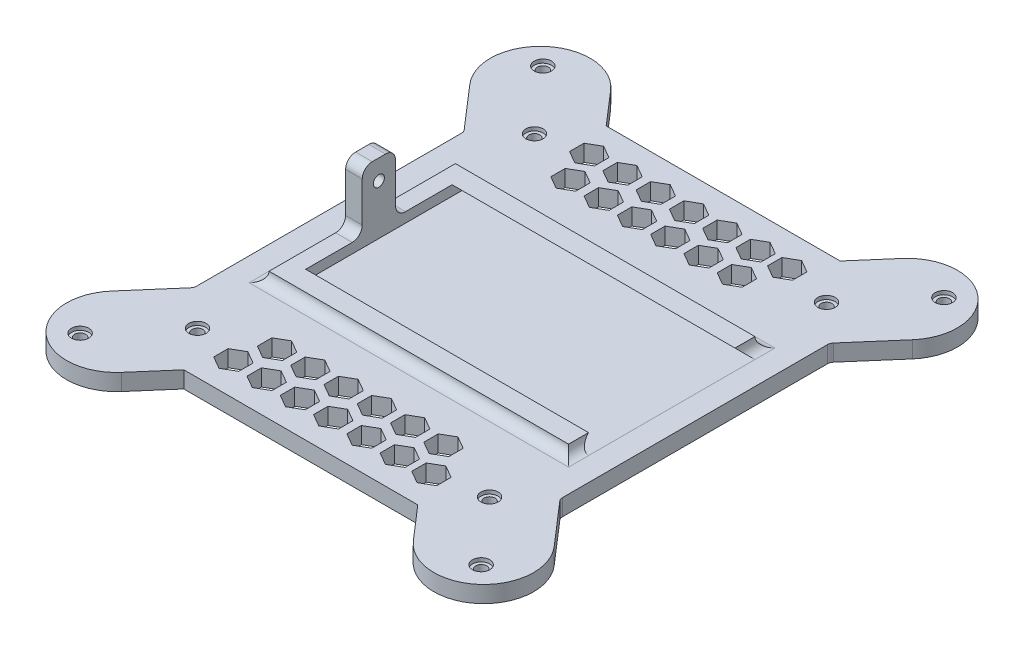
SolidWorks part; units mm, degrees
ref_plane "Front Plane" through (0, 0, 0) normal (0, 0, 1) x (1, 0, 0)
ref_plane "Top Plane" through (0, 0, 0) normal (0, 1, 0) x (1, 0, 0)
ref_plane "Right Plane" through (0, 0, 0) normal (1, 0, 0) x (0, 0, -1)
sketch "Sketch1" plane through (0, 0, 0) normal (0, 1, 0) x (1, 0, 0)
  line L0 (-53.6647, 84.824) -> (-76.3353, 65.176)
  line L1 (-65, 75) -> (65, 75) construction
  line L2 (-65, 75) -> (-65, -75) construction
  line L3 (-65, -75) -> (65, -75) construction
  line L4 (65, 75) -> (65, -75) construction
  line L5 (-65, 75) -> (65, -75) construction
  line L6 (-65, -75) -> (65, 75) construction
  line L7 (-76.3353, 65.176) -> (53.6647, -84.824)
  line L8 (53.6647, -84.824) -> (76.3353, -65.176)
  line L9 (76.3353, -65.176) -> (-53.6647, 84.824)
  line L10 (53.6647, 84.824) -> (76.3353, 65.176)
  line L11 (76.3353, 65.176) -> (-53.6647, -84.824)
  line L12 (-53.6647, -84.824) -> (-76.3353, -65.176)
  line L13 (-76.3353, -65.176) -> (53.6647, 84.824)
  line L15 (-55, -63.4615) -> (55, -63.4615)
  line L16 (-55, -63.4615) -> (-55, 63.4615)
  line L17 (-55, 63.4615) -> (55, 63.4615)
  line L18 (55, -63.4615) -> (55, 63.4615)
  line L19 (-55, -63.4615) -> (55, 63.4615) construction
  line L20 (-55, 63.4615) -> (55, -63.4615) construction
  point P0 (0, 0)
  point P12 (0, 0)
  dimension "D1" = 130
  dimension "D2" = 150
  dimension "D3" = 30
  dimension "D4" = 30
  dimension "D5" = 110
extrude "Boss-Extrude1" add sketch "Sketch1" along normal blind 5 contours L16 L17 L9 L0 L7 | L16 L13 L7 | L17 L16 L7 L13 L9 | L17 L9 L13 | L18 L11 L10 L13 L17 | L11 L18 L17 L13 L9 | L9 L18 L11 | L15 L18 L9 L11 L7 | L18 L15 L7 L8 L9 | L11 L15 L7 | L13 L7 L11 L9 | L16 L15 L11 L7 L13 | L15 L16 L13 L12 L11 region at (-57.5786, 0, -65.7171) region at (0, 0, -49.9421) region at (-30.0835, 0, -34.7117) region at (-43.2831, 0, 0) region at (30.0835, 0, -34.7117) region at (0, 0, 0) region at (57.5786, 0, -65.7171) region at (-30.0835, 0, 34.7117) region at (-57.5786, 0, 65.7171) region at (43.2831, 0, 0) region at (30.0835, 0, 34.7117) region at (0, 0, 49.9421) region at (57.5786, 0, 65.7171)
sketch "Sketch2" plane through (0, 0, 0) normal (0, -1, 0) x (1, 0, 0)
  line L0 (-65, 75) -> (65, -75) construction
  line L1 (-53.6647, 84.824) -> (-76.3353, 65.176) construction
  line L2 (53.6647, -84.824) -> (76.3353, -65.176) construction
  line L3 (65, 75) -> (-65, -75) construction
  line L4 (53.6647, 84.824) -> (76.3353, 65.176) construction
  line L5 (-53.6647, -84.824) -> (-76.3353, -65.176) construction
  circle A0 centre (-60.2536, 69.5234) radius 1.65
  circle A1 centre (-43.8803, 50.6312) radius 1.65
  circle A2 centre (60.2536, 69.5234) radius 1.65
  circle A3 centre (43.8803, 50.6312) radius 1.65
  circle A4 centre (60.2536, -69.5234) radius 1.65
  circle A5 centre (43.8803, -50.6312) radius 1.65
  circle A6 centre (-60.2536, -69.5234) radius 1.65
  circle A7 centre (-43.8803, -50.6312) radius 1.65
  point P43 (0, 0)
  dimension "D2" = 3.3
  dimension "D1" = 25
  dimension "D3" = 67
extrude "Cut-Extrude1" cut sketch "Sketch2" against normal up to surface (5 mm away) up to face at (0, 5, 0)
fillet "Fillet1" 2 edges at (76.3353, 2.5, 65.176) (53.6647, 2.5, 84.824) type full round first side face at (65.6677, 2.5, 52.8672) second side face at (44.4076, 2.5, 74.1427) middle face at (65, 2.5, 75)
fillet "Fillet2" 2 edges at (-53.6647, 2.5, 84.824) (-76.3353, 2.5, 65.176) type full round first side face at (-44.4076, 2.5, 74.1427) second side face at (-65.6677, 2.5, 52.8672) middle face at (-65, 2.5, 75)
fillet "Fillet3" 2 edges at (-76.3353, 2.5, -65.176) (-53.6647, 2.5, -84.824) type full round first side face at (-65.6677, 2.5, -52.8672) second side face at (-44.4076, 2.5, -74.1427) middle face at (-65, 2.5, -75)
fillet "Fillet4" 2 edges at (53.6647, 2.5, -84.824) (76.3353, 2.5, -65.176) type full round first side face at (44.4076, 2.5, -74.1427) second side face at (65.6677, 2.5, -52.8672) middle face at (65, 2.5, -75)
sketch "Sketch4" plane through (0, 5, 0) normal (0, 1, 0) x (1, 0, 0)
  circle A0 centre (-60.2536, 69.5234) radius 2.6
  circle A1 centre (-43.8803, 50.6312) radius 2.6
  circle A2 centre (43.8803, 50.6312) radius 2.6
  circle A3 centre (60.2536, 69.5234) radius 2.6
  circle A4 centre (43.8803, -50.6312) radius 2.6
  circle A5 centre (60.2536, -69.5234) radius 2.6
  circle A6 centre (-43.8803, -50.6312) radius 2.6
  circle A7 centre (-60.2536, -69.5234) radius 2.6
  dimension "D1" = 5.2
extrude "Cut-Extrude3" cut sketch "Sketch4" against normal blind 1.1
fillet "Fillet6" radius 2 4 edges at (55, 2.5, 40.5583) (55, 2.5, -40.5583) (-55, 2.5, -40.5583) (-55, 2.5, 40.5583)
sketch "Sketch8" plane through (55, 0, 0) normal (1, 0, 0) x (0, 0, -1)
  line L0 (-28, 8.0001) -> (-28, 5)
  line L1 (-39.8123, 5) -> (39.8123, 5) construction
  line L2 (-28, 5) -> (28, 5)
  line L3 (28, 5) -> (28, 8.0001)
  line L4 (28, 8.0001) -> (22, 8.0001)
  line L5 (22, 8.0001) -> (25, 5.0001)
  line L6 (25, 5.0001) -> (-25, 5.0001)
  line L7 (-25, 5.0001) -> (-22, 8.0001)
  line L8 (-22, 8.0001) -> (-28, 8.0001)
  line L11 (-39.8123, 0) -> (39.8123, 0) construction
  point P7 (0, 5.0001)
  point P15 (0, 0)
  dimension "D1" = 56
  dimension "D2" = 3.0001
  dimension "D3" = 45
  dimension "D4" = 45
  dimension "D5" = 3
  dimension "D6" = 3
  dimension "D7" = 3
  dimension "D8" = 3
extrude "Boss-Extrude3" add sketch "Sketch8" against normal blind 90 from offset 10 offset against normal yes
sketch "Sketch9" plane through (0, 0, -28) normal (0, 0, -1) x (-1, 0, 0)
  line L0 (45, 8.0001) -> (-45, 8.0001) construction
  line L1 (45, 5) -> (40, 5)
  line L2 (45, 5) -> (45, 8.0001)
  line L3 (45, 8.0001) -> (40, 8.0001)
  line L4 (40, 5) -> (40, 8.0001)
  line L5 (45, 5) -> (40, 8.0001) construction
  line L6 (45, 8.0001) -> (40, 5) construction
  line L7 (45, 5) -> (45, 8.0001) construction
  line L8 (45, 5) -> (-45, 5) construction
  point P0 (42.5, 6.5001)
  dimension "D1" = 5
extrude "Boss-Extrude4" add sketch "Sketch9" against normal up to surface (56 mm away) up to face at (0, 6.5, 28)
sketch "Sketch13" plane through (0, 5, 0) normal (0, 1, 0) x (1, 0, 0)
  line L0 (-55, -39.8123) -> (-55, 39.8123) construction
  line L1 (-26.5, 51.2965) -> (-26.5, 55.6266)
  line L2 (-26.5, 55.6266) -> (-30.25, 57.7917)
  line L3 (-30.25, 57.7917) -> (-34, 55.6266)
  line L4 (-34, 55.6266) -> (-34, 51.2965)
  line L5 (-34, 51.2965) -> (-30.25, 49.1314)
  line L6 (-30.25, 49.1314) -> (-26.5, 51.2965)
  line L13 (-35.1506, 63.4615) -> (35.1506, 63.4615) construction
  line L20 (-16.5, 51.2965) -> (-16.5, 55.6266)
  line L21 (-26.5, 39.7495) -> (-22.75, 41.9145)
  line L22 (-22.75, 41.9145) -> (-22.75, 46.2447)
  line L23 (-22.75, 46.2447) -> (-26.5, 48.4097)
  line L24 (-26.5, 48.4097) -> (-30.25, 46.2447)
  line L25 (-30.25, 46.2447) -> (-30.25, 41.9145)
  line L26 (-30.25, 41.9145) -> (-26.5, 39.7495)
  line L27 (-16.5, 55.6266) -> (-20.25, 57.7917)
  line L28 (-20.25, 57.7917) -> (-24, 55.6266)
  line L29 (-24, 55.6266) -> (-24, 51.2965)
  line L30 (-24, 51.2965) -> (-20.25, 49.1314)
  line L31 (-20.25, 49.1314) -> (-16.5, 51.2965)
  line L32 (-16.5, 39.7495) -> (-12.75, 41.9145)
  line L33 (-12.75, 41.9145) -> (-12.75, 46.2447)
  line L34 (-12.75, 46.2447) -> (-16.5, 48.4097)
  line L35 (-16.5, 48.4097) -> (-20.25, 46.2447)
  line L36 (-20.25, 46.2447) -> (-20.25, 41.9145)
  line L37 (-20.25, 41.9145) -> (-16.5, 39.7495)
  line L38 (-6.5, 51.2965) -> (-6.5, 55.6266)
  line L39 (-6.5, 55.6266) -> (-10.25, 57.7917)
  line L40 (-10.25, 57.7917) -> (-14, 55.6266)
  line L41 (-14, 55.6266) -> (-14, 51.2965)
  line L42 (-14, 51.2965) -> (-10.25, 49.1314)
  line L43 (-10.25, 49.1314) -> (-6.5, 51.2965)
  line L44 (-6.5, 39.7495) -> (-2.75, 41.9145)
  line L45 (-2.75, 41.9145) -> (-2.75, 46.2447)
  line L46 (-2.75, 46.2447) -> (-6.5, 48.4097)
  line L47 (-6.5, 48.4097) -> (-10.25, 46.2447)
  line L48 (-10.25, 46.2447) -> (-10.25, 41.9145)
  line L49 (-10.25, 41.9145) -> (-6.5, 39.7495)
  line L50 (3.5, 51.2965) -> (3.5, 55.6266)
  line L51 (3.5, 55.6266) -> (-0.25, 57.7917)
  line L52 (-0.25, 57.7917) -> (-4, 55.6266)
  line L53 (-4, 55.6266) -> (-4, 51.2965)
  line L54 (-4, 51.2965) -> (-0.25, 49.1314)
  line L55 (-0.25, 49.1314) -> (3.5, 51.2965)
  line L56 (3.5, 39.7495) -> (7.25, 41.9145)
  line L57 (7.25, 41.9145) -> (7.25, 46.2447)
  line L58 (7.25, 46.2447) -> (3.5, 48.4097)
  line L59 (3.5, 48.4097) -> (-0.25, 46.2447)
  line L60 (-0.25, 46.2447) -> (-0.25, 41.9145)
  line L61 (-0.25, 41.9145) -> (3.5, 39.7495)
  line L62 (13.5, 51.2965) -> (13.5, 55.6266)
  line L63 (13.5, 55.6266) -> (9.75, 57.7917)
  line L64 (9.75, 57.7917) -> (6, 55.6266)
  line L65 (6, 55.6266) -> (6, 51.2965)
  line L66 (6, 51.2965) -> (9.75, 49.1314)
  line L67 (9.75, 49.1314) -> (13.5, 51.2965)
  line L68 (13.5, 39.7495) -> (17.25, 41.9145)
  line L69 (17.25, 41.9145) -> (17.25, 46.2447)
  line L70 (17.25, 46.2447) -> (13.5, 48.4097)
  line L71 (13.5, 48.4097) -> (9.75, 46.2447)
  line L72 (9.75, 46.2447) -> (9.75, 41.9145)
  line L73 (9.75, 41.9145) -> (13.5, 39.7495)
  line L74 (23.5, 51.2965) -> (23.5, 55.6266)
  line L75 (23.5, 55.6266) -> (19.75, 57.7917)
  line L76 (19.75, 57.7917) -> (16, 55.6266)
  line L77 (16, 55.6266) -> (16, 51.2965)
  line L78 (16, 51.2965) -> (19.75, 49.1314)
  line L79 (19.75, 49.1314) -> (23.5, 51.2965)
  line L80 (23.5, 39.7495) -> (27.25, 41.9145)
  line L81 (27.25, 41.9145) -> (27.25, 46.2447)
  line L82 (27.25, 46.2447) -> (23.5, 48.4097)
  line L83 (23.5, 48.4097) -> (19.75, 46.2447)
  line L84 (19.75, 46.2447) -> (19.75, 41.9145)
  line L85 (19.75, 41.9145) -> (23.5, 39.7495)
  line L86 (0, 0) -> (-20, 0) construction
  line L87 (33, 51.2965) -> (33, 55.6266)
  line L88 (33, 55.6266) -> (29.25, 57.7917)
  line L89 (29.25, 57.7917) -> (25.5, 55.6266)
  line L90 (25.5, 55.6266) -> (25.5, 51.2965)
  line L91 (25.5, 51.2965) -> (29.25, 49.1314)
  line L92 (29.25, 49.1314) -> (33, 51.2965)
  line L93 (29.25, -49.1314) -> (33, -51.2965)
  line L94 (25.5, -51.2965) -> (29.25, -49.1314)
  line L95 (25.5, -55.6266) -> (25.5, -51.2965)
  line L96 (29.25, -57.7917) -> (25.5, -55.6266)
  line L97 (33, -55.6266) -> (29.25, -57.7917)
  line L98 (33, -51.2965) -> (33, -55.6266)
  line L99 (19.75, -41.9145) -> (23.5, -39.7495)
  line L100 (19.75, -46.2447) -> (19.75, -41.9145)
  line L101 (23.5, -48.4097) -> (19.75, -46.2447)
  line L102 (27.25, -46.2447) -> (23.5, -48.4097)
  line L103 (27.25, -41.9145) -> (27.25, -46.2447)
  line L104 (23.5, -39.7495) -> (27.25, -41.9145)
  line L105 (19.75, -49.1314) -> (23.5, -51.2965)
  line L106 (16, -51.2965) -> (19.75, -49.1314)
  line L107 (16, -55.6266) -> (16, -51.2965)
  line L108 (19.75, -57.7917) -> (16, -55.6266)
  line L109 (23.5, -55.6266) -> (19.75, -57.7917)
  line L110 (23.5, -51.2965) -> (23.5, -55.6266)
  line L111 (9.75, -41.9145) -> (13.5, -39.7495)
  line L112 (9.75, -46.2447) -> (9.75, -41.9145)
  line L113 (13.5, -48.4097) -> (9.75, -46.2447)
  line L114 (17.25, -46.2447) -> (13.5, -48.4097)
  line L115 (17.25, -41.9145) -> (17.25, -46.2447)
  line L116 (13.5, -39.7495) -> (17.25, -41.9145)
  line L117 (9.75, -49.1314) -> (13.5, -51.2965)
  line L118 (6, -51.2965) -> (9.75, -49.1314)
  line L119 (6, -55.6266) -> (6, -51.2965)
  line L120 (9.75, -57.7917) -> (6, -55.6266)
  line L121 (13.5, -55.6266) -> (9.75, -57.7917)
  line L122 (13.5, -51.2965) -> (13.5, -55.6266)
  line L123 (-0.25, -41.9145) -> (3.5, -39.7495)
  line L124 (-0.25, -46.2447) -> (-0.25, -41.9145)
  line L125 (3.5, -48.4097) -> (-0.25, -46.2447)
  line L126 (7.25, -46.2447) -> (3.5, -48.4097)
  line L127 (7.25, -41.9145) -> (7.25, -46.2447)
  line L128 (3.5, -39.7495) -> (7.25, -41.9145)
  line L129 (-0.25, -49.1314) -> (3.5, -51.2965)
  line L130 (-4, -51.2965) -> (-0.25, -49.1314)
  line L131 (-4, -55.6266) -> (-4, -51.2965)
  line L132 (-0.25, -57.7917) -> (-4, -55.6266)
  line L133 (3.5, -55.6266) -> (-0.25, -57.7917)
  line L134 (3.5, -51.2965) -> (3.5, -55.6266)
  line L135 (-10.25, -41.9145) -> (-6.5, -39.7495)
  line L136 (-10.25, -46.2447) -> (-10.25, -41.9145)
  line L137 (-6.5, -48.4097) -> (-10.25, -46.2447)
  line L138 (-2.75, -46.2447) -> (-6.5, -48.4097)
  line L139 (-2.75, -41.9145) -> (-2.75, -46.2447)
  line L140 (-6.5, -39.7495) -> (-2.75, -41.9145)
  line L141 (-10.25, -49.1314) -> (-6.5, -51.2965)
  line L142 (-14, -51.2965) -> (-10.25, -49.1314)
  line L143 (-14, -55.6266) -> (-14, -51.2965)
  line L144 (-10.25, -57.7917) -> (-14, -55.6266)
  line L145 (-6.5, -55.6266) -> (-10.25, -57.7917)
  line L146 (-6.5, -51.2965) -> (-6.5, -55.6266)
  line L147 (-20.25, -41.9145) -> (-16.5, -39.7495)
  line L148 (-20.25, -46.2447) -> (-20.25, -41.9145)
  line L149 (-16.5, -48.4097) -> (-20.25, -46.2447)
  line L150 (-12.75, -46.2447) -> (-16.5, -48.4097)
  line L151 (-12.75, -41.9145) -> (-12.75, -46.2447)
  line L152 (-16.5, -39.7495) -> (-12.75, -41.9145)
  line L153 (-20.25, -49.1314) -> (-16.5, -51.2965)
  line L154 (-24, -51.2965) -> (-20.25, -49.1314)
  line L155 (-24, -55.6266) -> (-24, -51.2965)
  line L156 (-20.25, -57.7917) -> (-24, -55.6266)
  line L157 (-16.5, -55.6266) -> (-20.25, -57.7917)
  line L158 (-30.25, -41.9145) -> (-26.5, -39.7495)
  line L159 (-30.25, -46.2447) -> (-30.25, -41.9145)
  line L160 (-26.5, -48.4097) -> (-30.25, -46.2447)
  line L161 (-22.75, -46.2447) -> (-26.5, -48.4097)
  line L162 (-22.75, -41.9145) -> (-22.75, -46.2447)
  line L163 (-26.5, -39.7495) -> (-22.75, -41.9145)
  line L164 (-16.5, -51.2965) -> (-16.5, -55.6266)
  line L165 (-30.25, -49.1314) -> (-26.5, -51.2965)
  line L166 (-34, -51.2965) -> (-30.25, -49.1314)
  line L167 (-34, -55.6266) -> (-34, -51.2965)
  line L168 (-30.25, -57.7917) -> (-34, -55.6266)
  line L169 (-26.5, -55.6266) -> (-30.25, -57.7917)
  line L170 (-26.5, -51.2965) -> (-26.5, -55.6266)
  circle A0 centre (-30.25, 53.4615) radius 3.75 construction
  circle A1 centre (-26.5, 44.0796) radius 3.75 construction
  circle A2 centre (-20.25, 53.4615) radius 3.75 construction
  circle A3 centre (-16.5, 44.0796) radius 3.75 construction
  circle A4 centre (-10.25, 53.4615) radius 3.75 construction
  circle A5 centre (-6.5, 44.0796) radius 3.75 construction
  circle A6 centre (-0.25, 53.4615) radius 3.75 construction
  circle A7 centre (3.5, 44.0796) radius 3.75 construction
  circle A8 centre (9.75, 53.4615) radius 3.75 construction
  circle A9 centre (13.5, 44.0796) radius 3.75 construction
  circle A10 centre (19.75, 53.4615) radius 3.75 construction
  circle A11 centre (23.5, 44.0796) radius 3.75 construction
  circle A12 centre (29.25, 53.4615) radius 3.75 construction
  circle A13 centre (29.25, -53.4615) radius 3.75 construction
  circle A14 centre (23.5, -44.0796) radius 3.75 construction
  circle A15 centre (19.75, -53.4615) radius 3.75 construction
  circle A16 centre (13.5, -44.0796) radius 3.75 construction
  circle A17 centre (9.75, -53.4615) radius 3.75 construction
  circle A18 centre (3.5, -44.0796) radius 3.75 construction
  circle A19 centre (-0.25, -53.4615) radius 3.75 construction
  circle A20 centre (-6.5, -44.0796) radius 3.75 construction
  circle A21 centre (-10.25, -53.4615) radius 3.75 construction
  circle A22 centre (-16.5, -44.0796) radius 3.75 construction
  circle A23 centre (-20.25, -53.4615) radius 3.75 construction
  circle A24 centre (-26.5, -44.0796) radius 3.75 construction
  circle A25 centre (-30.25, -53.4615) radius 3.75 construction
  point P10 (-28.375, 47.3272)
  point P22 (25.375, 47.3272)
  dimension "D1" = 7.5
  dimension "D2" = 10
  dimension "D3" = 21
  dimension "D4" = 2.5
  dimension "D6" = 10
  dimension "D7" = 2
  dimension "D8" = 3.5
  dimension "D9" = 20
  dimension "D5" = 6
extrude "Cut-Extrude7" cut sketch "Sketch13" against normal up to surface (5 mm away) up to face at (60.2536, 0, -71.1734)
sketch "Sketch15" plane through (-45, 0, 0) normal (-1, 0, 0) x (0, 0, 1)
  line L0 (-28, 8.0001) -> (28, 8.0001) construction
  line L1 (-5, 26.0001) -> (5, 26.0001)
  line L2 (-5, 26.0001) -> (-5, 8.0001)
  line L3 (-5, 8.0001) -> (5, 8.0001)
  line L4 (5, 26.0001) -> (5, 8.0001)
  line L5 (-5, 26.0001) -> (5, 8.0001) construction
  line L6 (-5, 8.0001) -> (5, 26.0001) construction
  circle A1 centre (0, 20.0001) radius 1.65
  point P0 (0, 17.0001)
  dimension "D3" = 12
  dimension "D4" = 3.3
  dimension "D1" = 10
  dimension "D2" = 18
extrude "Boss-Extrude5" add sketch "Sketch15" against normal up to surface (5 mm away) up to face at (-40, 6.5001, 0)
fillet "Fillet7" radius 3 8 edges at (-42.5, 26.0001, 5) (-42.5, 26.0001, -5) (45, 5, 0) (0, 5, 28) (0, 5, -28) (-45, 5, 0) (-42.5, 8.0001, -5) (-42.5, 8.0001, 5)
sketch "Sketch16" plane through (0, 0, 0) normal (0, -1, 0) x (1, 0, 0)
  line L1 (45, -35) -> (-45, -35)
  line L2 (45, -35) -> (45, 35)
  line L3 (45, 35) -> (-45, 35)
  line L4 (-45, -35) -> (-45, 35)
  line L5 (45, -35) -> (-45, 35) construction
  line L6 (45, 35) -> (-45, -35) construction
  point P0 (0, 0)
  dimension "D1" = 90
  dimension "D2" = 70
extrude "Cut-Extrude8" cut sketch "Sketch16" against normal blind 2
fillet "Fillet8" radius 5 4 edges at (0, 2, 35) (45, 2, 0) (0, 2, -35) (-45, 2, 0)
fillet "Fillet9" radius 5 4 edges at (-45, 0, 0) (0, 0, -35) (0, 0, 35) (45, 0, 0)
